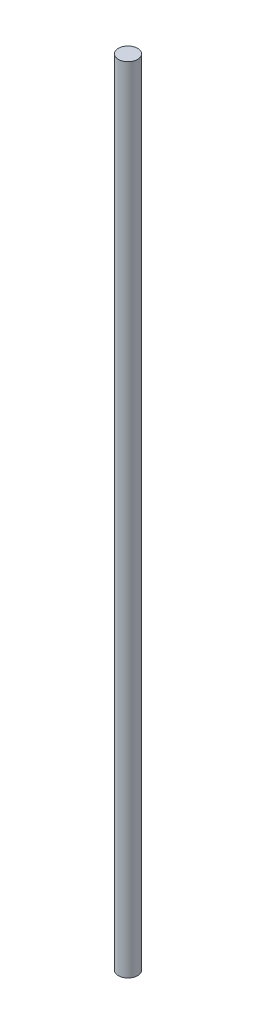
SolidWorks part; units mm, degrees
ref_plane "Front Plane" through (0, 0, 0) normal (0, 0, 1) x (1, 0, 0)
ref_plane "Top Plane" through (0, 0, 0) normal (0, 1, 0) x (1, 0, 0)
ref_plane "Right Plane" through (0, 0, 0) normal (1, 0, 0) x (0, 0, -1)
sketch "Sketch1" plane through (0, 0, 0) normal (0, 1, 0) x (1, 0, 0)
  circle A0 centre (0, 0) radius 4
  dimension "D1" = 8
extrude "Boss-Extrude1" add sketch "Sketch1" along normal blind 330
sketch "Sketch2" plane through (0, 0, 0) normal (0, 0, 1) x (1, 0, 0)
  line L0 (-2.3135, 225.9429) -> (1.5978, 225.9429)
  line L1 (-2.3135, 325.9429) -> (1.5978, 325.9429)
  line L2 (-2.3135, 325.9429) -> (-2.3135, 321.8615)
  line L3 (-2.3135, 321.8615) -> (1.5978, 321.8615)
  line L4 (1.5978, 325.9429) -> (1.5978, 321.8615)
  line L5 (-2.3135, 225.9429) -> (-2.3135, 221.8615)
  line L6 (-2.3135, 221.8615) -> (1.5978, 221.8615)
  line L7 (1.5978, 225.9429) -> (1.5978, 221.8615)
  line L8 (-2.3135, 125.9429) -> (1.5978, 125.9429)
  line L9 (-2.3135, 125.9429) -> (-2.3135, 121.8615)
  line L10 (-2.3135, 121.8615) -> (1.5978, 121.8615)
  line L11 (1.5978, 125.9429) -> (1.5978, 121.8615)
  line L12 (-2.3135, 25.9429) -> (1.5978, 25.9429)
  line L13 (-2.3135, 25.9429) -> (-2.3135, 21.8615)
  line L14 (-2.3135, 21.8615) -> (1.5978, 21.8615)
  line L15 (1.5978, 25.9429) -> (1.5978, 21.8615)
  dimension "D1" = 4
extrude "Cut-Extrude1" cut sketch "Sketch2" against normal blind 10 from offset 3.5 offset against normal yes
